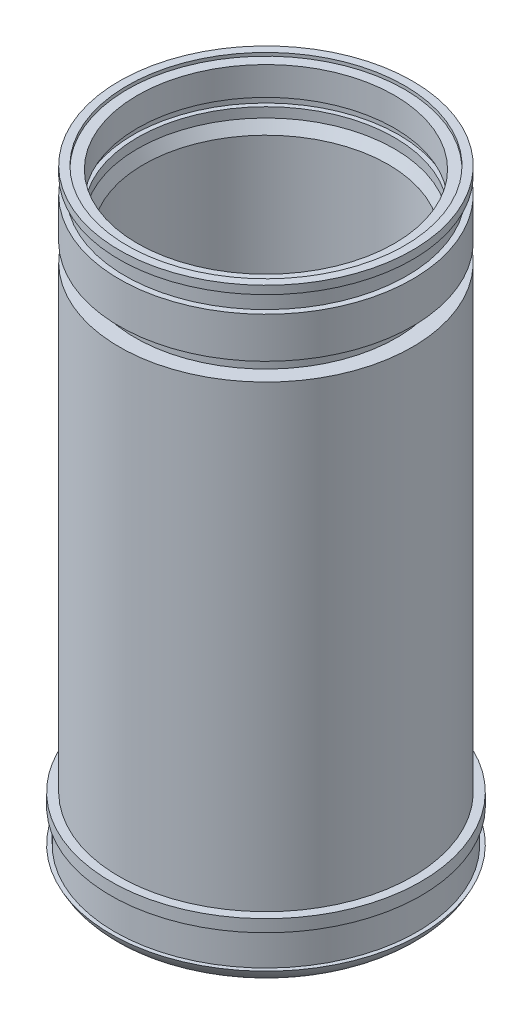
SolidWorks part; units mm, degrees
material "PVC"
ref_plane "Front Plane" through (0, 0, 0) normal (0, 0, 1) x (1, 0, 0)
ref_plane "Top Plane" through (0, 0, 0) normal (0, 1, 0) x (1, 0, 0)
ref_plane "Right Plane" through (0, 0, 0) normal (1, 0, 0) x (0, 0, -1)
sketch "Sketch1" plane through (0, 0, 0) normal (0, 0, 1) x (1, 0, 0)
  line L0 (0, 0) -> (0, 64.0047) construction
  line L1 (28.7274, 7.9375) -> (29.3687, 7.9375)
  line L2 (29.3687, 7.9375) -> (29.3687, 0)
  line L3 (60.3885, 20.6375) -> (58.8645, 20.6375)
  line L4 (58.8645, 20.6375) -> (58.8645, 7.6835)
  line L5 (28.7274, 7.9375) -> (28.7274, 11.1125)
  line L6 (28.7274, 11.1125) -> (34.925, 11.1125)
  line L7 (34.925, 11.1125) -> (34.925, 18.0975)
  line L8 (34.925, 18.0975) -> (28.7274, 18.0975)
  line L9 (28.7274, 18.0975) -> (28.7274, 19.685)
  line L10 (28.7274, 19.685) -> (30.9499, 19.685)
  line L11 (30.9499, 19.685) -> (30.9499, 26.289)
  line L12 (30.9499, 26.289) -> (28.7274, 26.289)
  line L13 (28.7274, 26.289) -> (28.7274, 26.9875)
  line L14 (58.8645, 7.6835) -> (60.3885, 7.6835)
  line L15 (47.625, 30.1625) -> (47.625, 213.1834)
  line L16 (50, 235.331) -> (53.975, 235.331)
  line L17 (57.0611, 236.601) -> (57.0611, 233.426)
  line L18 (57.0611, 233.426) -> (54.8386, 233.426)
  line L19 (54.8386, 233.426) -> (54.8386, 226.822)
  line L20 (54.8386, 226.822) -> (57.0611, 226.822)
  line L21 (57.0611, 226.822) -> (57.0611, 210.947)
  line L22 (57.0611, 210.947) -> (50.8635, 210.947)
  line L23 (50.8635, 210.947) -> (50.8635, 203.962)
  line L24 (50.8635, 203.962) -> (57.0611, 203.962)
  line L25 (57.0611, 203.962) -> (57.0611, 197.612)
  line L26 (60.3885, 7.6835) -> (60.3885, 0)
  line L27 (28.7274, 7.9375) -> (28.7274, 0) construction
  line L28 (28.7274, 0) -> (29.3687, 0) construction
  line L29 (50, 217.297) -> (47.625, 213.1834)
  line L30 (57.0611, 25.4) -> (60.3885, 25.4)
  line L31 (60.3885, 25.4) -> (60.3885, 20.6375)
  line L32 (60.3885, 0) -> (29.3687, 0)
  line L33 (57.2135, 25.4) -> (57.2135, 187.6762) construction
  line L34 (57.15, 25.4) -> (57.15, 204.5362) construction
  line L35 (28.575, 0) -> (28.575, 28.0987) construction
  line L36 (28.5496, 0) -> (28.5496, 28.0987) construction
  line L37 (57.0611, 197.612) -> (47.625, 197.612) construction
  line L38 (50, 235.331) -> (50, 224.257)
  line L39 (50, 224.257) -> (51.75, 224.257)
  line L40 (51.75, 224.257) -> (51.75, 221.107)
  line L41 (51.75, 221.107) -> (50, 221.107)
  line L42 (50, 221.107) -> (50, 217.297)
  line L43 (50, 217.297) -> (47.6885, 217.297) construction
  line L44 (28.7274, 26.9875) -> (47.625, 30.1625)
  line L48 (57.0611, 197.612) -> (57.0611, 25.4)
  line L51 (53.975, 235.331) -> (53.975, 236.601)
  line L52 (53.975, 236.601) -> (57.0611, 236.601)
  dimension "D2" = 25.4
  dimension "D4" = 2.3749
  dimension "D5" = 114.427
  dimension "D6" = 100
  dimension "D7" = 95.25
  dimension "D8" = 114.3
  dimension "D9" = 6.604
  dimension "D10" = 2.3749
  dimension "D11" = 0.1524
  dimension "D12" = 57.15
  dimension "D13" = 57.0992
  dimension "D14" = 0.1524
  dimension "D15" = 101.727
  dimension "D16" = 30.1625
  dimension "D17" = 7.9375
  dimension "D18" = 6.35
  dimension "D19" = 172.212
  dimension "D20" = 6.985
  dimension "D21" = 6.35
  dimension "D22" = 1.5875
  dimension "D23" = 6.985
  dimension "D24" = 6.35
  dimension "D25" = 15.875
  dimension "D26" = 0.7937
  dimension "D27" = 103.5
  dimension "D28" = 3.81
  dimension "D29" = 3.175
  dimension "D30" = 3.15
  dimension "D31" = 3.175
  dimension "D32" = 3.175
  dimension "D33" = 3.2385
  dimension "D34" = 26.9875
  dimension "D35" = 0.6985
  dimension "D36" = 12.954
  dimension "D37" = 1.524
  dimension "D38" = 6.35
  dimension "D39" = 3.175
  dimension "D40" = 4.7625
  dimension "D41" = 30
  dimension "D42" = 1.27
  dimension "D43" = 107.95
revolve "Revolve1" add sketch "Sketch1" angle 360 about L0
ref_axis "Axis1" through (0, 292.3641, 0) along (0, -1, 0)
fillet "Fillet1" radius 3.175 1 edges at (0, 30.1625, -47.625)
sketch "Strip brush" plane through (0, 0, 0) normal (0, 0, 1) x (1, 0, 0)
  line L0 (0, 0) -> (0, 278.442) construction
  line L1 (0, 292.3641) -> (0, -13.9221) construction
  line L2 (45.1866, 80.391) -> (45.1866, 74.803)
  line L3 (45.1866, 74.803) -> (49.7586, 74.803)
  line L4 (49.7586, 74.803) -> (49.7586, 76.2)
  line L5 (49.7586, 76.2) -> (52.2986, 76.2)
  line L6 (45.1866, 80.391) -> (49.7586, 80.391)
  line L7 (49.7586, 80.391) -> (49.7586, 78.994)
  line L8 (49.7586, 78.994) -> (52.2986, 78.994)
  line L9 (52.2986, 76.2) -> (52.2986, 25.4)
  line L10 (52.2986, 25.4) -> (57.0611, 25.4)
  line L11 (57.0611, 25.4) -> (57.0611, 203.962) construction
  line L12 (52.2986, 78.994) -> (57.0611, 78.994)
  line L13 (57.0611, 78.994) -> (57.0611, 25.4)
  line L15 (60.3885, 25.4) -> (-60.3885, 25.4) construction
  dimension "D1" = 5.588
  dimension "D2" = 2.794
  dimension "D3" = 4.572
  dimension "D4" = 4.7625
  dimension "D5" = 50.8
  dimension "D7" = 2.54
revolve "Brush_1_" [suppressed] cut sketch "Strip brush" angle 360 about L0
fillet "Fillet3" [suppressed] radius 3.175
sketch "Sketch4" [suppressed] plane through (0, 0, 0) normal (0, 0, 1) x (1, 0, 0)
  line L0 (0, 0) -> (0, 276.4709) construction
  line L1 (0, 292.3641) -> (0, -13.9221) construction
  line L2 (-60.325, 0) -> (60.325, 0) construction
  line L3 (42.2843, 0) -> (47.0468, 0)
  line L4 (42.2843, 0) -> (42.2843, 29.6801)
  line L5 (42.2843, 29.6801) -> (47.0468, 29.6801)
  line L6 (47.0468, 0) -> (47.0468, 29.6801)
  line L7 (0, -3.175) -> (25.4, -3.175) construction
  line L8 (-30.8356, 0) -> (30.8356, 0) construction
  line L9 (25.4, -3.175) -> (36.0542, -3.175) construction
  line L10 (44.6656, 5.4364) -> (44.6656, 29.6801) construction
  arc A0 (36.0542, -3.175) -> (44.6656, 5.4364) centre (36.0542, 5.4364) ccw construction
  dimension "D1" = 50.8
  dimension "D2" = 3.175
  dimension "D3" = 4.7625
revolve "Brush_2_Cut-Revolve3" [suppressed] cut sketch "Sketch4" angle 360 about L0
fillet "Fillet4" [suppressed] radius 6.35
sketch "Sketch5" plane through (0, 25.4, 0) normal (0, 1, 0) x (1, 0, 0)
  circle A0 centre (0, 0) radius 73.4985
  circle A1 centre (0, 0) radius 57.785
  dimension "D1" = 115.57
extrude "FEA Cut-Extrude1" [suppressed] cut sketch "Sketch5" against normal blind 0.0254
sketch "Sketch2" plane through (0, 0, 0) normal (0, 1, 0) x (1, 0, 0)
  line L0 (0, 0) -> (60.3885, 0)
  line L1 (0, 0) -> (0, -60.3885)
  arc A0 (60.3885, 0) -> (0, -60.3885) centre (0, 0) ccw
  circle A1 centre (0, 0) radius 60.3885 construction
extrude "Slice for FEA" [suppressed] cut sketch "Sketch2" along normal through all
fillet "Fillet5" radius 12.7 1 edges at (0, 0, -60.3885)
fillet "Fillet6" radius 3.175 1 edges at (0, 0, -29.3687)
sketch "Sketch6" [suppressed] plane through (0, 245.872, 0) normal (0, 1, 0) x (1, 0, 0)
  circle A0 centre (0, 0) radius 56.8833
  circle A1 centre (0, 0) radius 56.8833 construction
extrude "Boss-Extrude1" [suppressed] add sketch "Sketch6" against normal up to surface (229.362 mm away)
